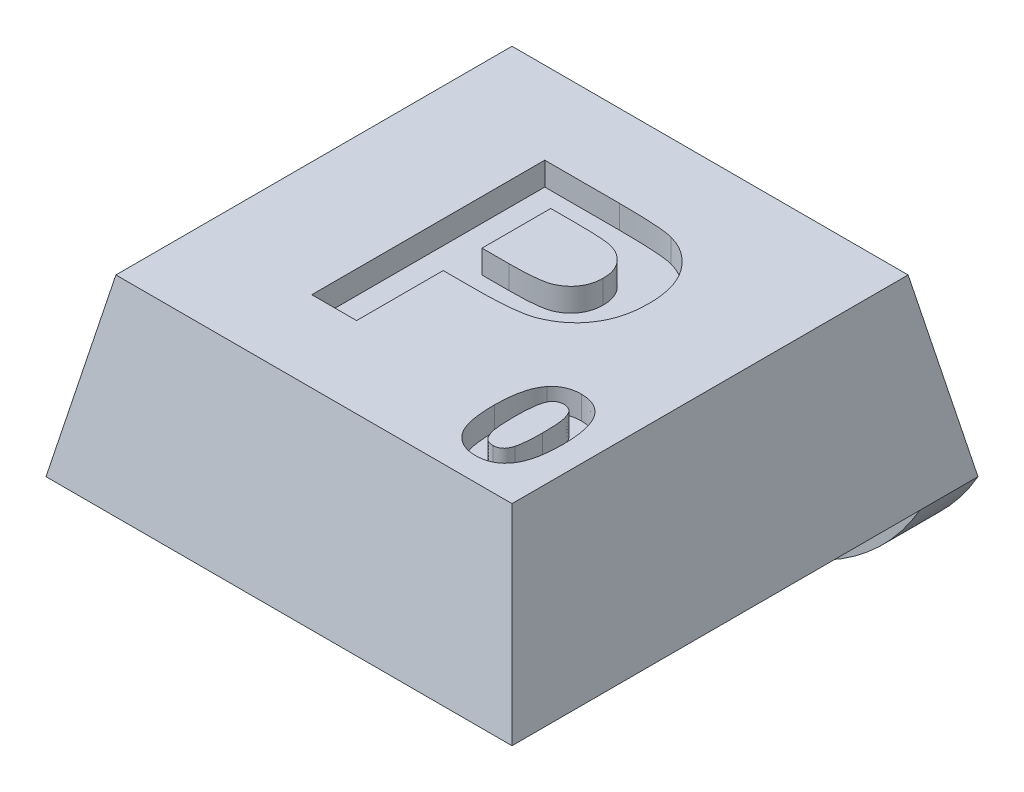
SolidWorks part; units mm, degrees
ref_plane "Front Plane" through (0, 0, 0) normal (0, 0, 1) x (1, 0, 0)
ref_plane "Top Plane" through (0, 0, 0) normal (0, 1, 0) x (1, 0, 0)
ref_plane "Right Plane" through (0, 0, 0) normal (1, 0, 0) x (0, 0, -1)
sketch "Sketch1" plane through (0, 0, 0) normal (0, 1, 0) x (1, 0, 0)
  line L1 (0, 0) -> (8, 0)
  line L2 (0, 0) -> (0, 8)
  line L3 (0, 8) -> (8, 8)
  line L4 (8, 0) -> (8, 8)
  dimension "D1" = 8
  dimension "D2" = 8
extrude "Boss-Extrude1" add sketch "Sketch1" along normal blind 3
sketch "Sketch2" plane through (0, 0, 0) normal (0, 0, 1) x (1, 0, 0)
  line L0 (0, 0) -> (0.6, 3)
  line L1 (0, 3) -> (8, 3) construction
  line L2 (0.6, 3) -> (0, 3)
  line L3 (0, 3) -> (0, 0)
  line L4 (8, 0) -> (7.4, 3)
  line L5 (7.4, 3) -> (8, 3)
  line L6 (8, 3) -> (8, 0)
  dimension "D1" = 0.6
  dimension "D2" = 0.6
extrude "Cut-Extrude1" cut sketch "Sketch2" against normal through all both and the other way through all
sketch "Sketch3" plane through (0, 0, 0) normal (1, 0, 0) x (0, 0, -1)
  line L0 (0, 0) -> (0.6, 3)
  line L1 (8, 3) -> (0, 3) construction
  line L2 (0.6, 3) -> (0, 3)
  line L3 (0, 3) -> (0, 0)
  line L4 (8, 3) -> (7.4, 3)
  line L5 (7.4, 3) -> (8, 0)
  line L6 (8, 3) -> (8, 0)
  dimension "D1" = 0.6
  dimension "D2" = 0.6
extrude "Cut-Extrude2" cut sketch "Sketch3" along normal blind 11
sketch "Sketch4" plane through (0, 0, 0) normal (0, -1, 0) x (1, 0, 0)
  line L0 (8, 0) -> (8, -8) construction
  line L3 (0, 0) -> (8, 0) construction
  circle A0 centre (4, -3.75) radius 1.8
  dimension "D1" = 3.6
  dimension "D2" = 4
  dimension "D3" = 3.75
extrude "Cut-Extrude3" cut sketch "Sketch4" against normal blind 0.8
sketch "Sketch5" plane through (0, 0, 0) normal (0, -1, 0) x (1, 0, 0)
  line L0 (8, 0) -> (8, -8) construction
  line L1 (0, -8) -> (8, -8)
  line L2 (0, -8) -> (0, -7)
  line L3 (0, -7) -> (8, -7)
  line L4 (8, -8) -> (8, -7)
  dimension "D1" = 1
extrude "Boss-Extrude2" add sketch "Sketch5" along normal blind 2
fillet "Fillet1" radius 4 2 edges at (8, -2, -7.5) (0, -2, -7.5)
sketch "Sketch6" plane through (0, 3, 0) normal (0, 1, 0) x (1, 0, 0)
  text T0 "P" font "Arial" height 4
extrude "Cut-Extrude4" cut sketch "Sketch6" against normal blind 0.4
sketch "Sketch7" plane through (0, 3, 0) normal (0, 1, 0) x (1, 0, 0)
  text T0 "0" font "Arial" height 1.8
extrude "Cut-Extrude5" cut sketch "Sketch7" against normal blind 0.4
